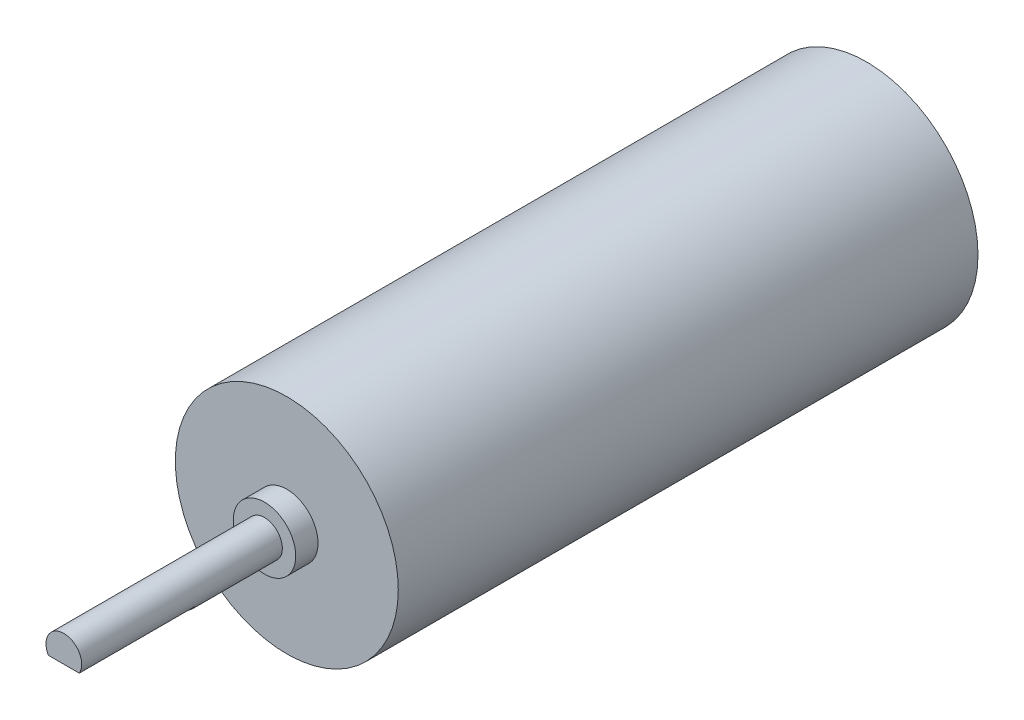
SolidWorks part; units mm, degrees
ref_plane "Plan de face" through (0, 0, 0) normal (0, 0, 1) x (1, 0, 0)
ref_plane "Plan de dessus" through (0, 0, 0) normal (0, 1, 0) x (1, 0, 0)
ref_plane "Plan de droite" through (0, 0, 0) normal (1, 0, 0) x (0, 0, -1)
sketch "Esquisse1" plane through (0, 0, 0) normal (0, 0, 1) x (1, 0, 0)
  circle A0 centre (0, 0) radius 12.5
  dimension "D1" = 25
extrude "Boss.-Extru.1" add sketch "Esquisse1" against normal blind 65
sketch "Esquisse2" plane through (0, 0, 0) normal (0, 0, 1) x (1, 0, 0)
  circle A0 centre (0, 0) radius 3.5
  dimension "D1" = 7
extrude "Boss.-Extru.2" add sketch "Esquisse2" along normal blind 2.5
sketch "Esquisse3" plane through (0, 0, 2.5) normal (0, 0, 1) x (1, 0, 0)
  circle A0 centre (0, 0) radius 2
  dimension "D1" = 4
extrude "Boss.-Extru.3" add sketch "Esquisse3" along normal blind 22.5
sketch "Esquisse4" plane through (0, 0, 25) normal (0, 0, 1) x (1, 0, 0)
  line L0 (-1.7321, -1) -> (1.7321, -1)
  line L1 (0, 2) -> (-2, 2) construction
  circle A0 centre (0, 0) radius 2 construction
  circle A1 centre (0, 0) radius 2 construction
  arc A2 (-1.7321, -1) -> (1.7321, -1) centre (0, 0) ccw
  point P8 (1.6426, -1.141)
  dimension "D1" = 3
extrude "Enlèv. mat.-Extru.1" cut sketch "Esquisse4" against normal blind 13
ref_axis "Axe1" through (0, 0, -65) along (0, 0, 1)
